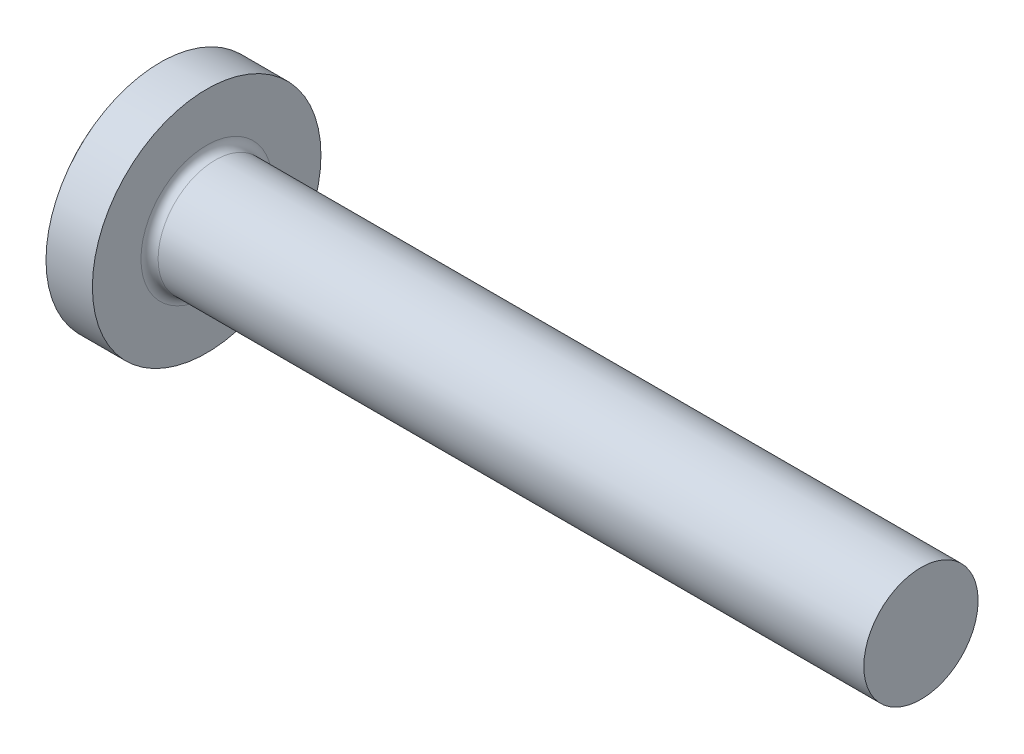
SolidWorks part; units mm, degrees
ref_plane "Front Plane" through (0, 0, 0) normal (0, 0, 1) x (1, 0, 0)
ref_plane "Top Plane" through (0, 0, 0) normal (0, 1, 0) x (1, 0, 0)
ref_plane "Right Plane" through (0, 0, 0) normal (1, 0, 0) x (0, 0, -1)
sketch "BodySke" plane through (0, 0, 0) normal (0, 0, 1) x (1, 0, 0)
  line L0 (0, 0) -> (111.3824, 0) construction
  line L1 (0, 0) -> (0, 8) construction
  line L2 (6, 4) -> (6, 8)
  line L3 (6, 8) -> (2.753, 8)
  line L4 (6, 4) -> (56, 4)
  line L5 (56, 4) -> (56, 0)
  line L6 (7.25, 7.824) -> (7.25, -6.8939) construction
  line L7 (0, 0) -> (56, 0)
  line L8 (8.5, 8.824) -> (8.5, -4.958) construction
  arc A1 (2.753, 8) -> (0, 0) centre (13, 0) ccw
  point P10 (56, 3.4455)
  dimension "Thread_minor" = 6.891
  dimension "Head_height" = 6
  dimension "Advance" = 1.25
  dimension "Length" = 50
  dimension "Head_dia" = 16
revolve "BaseBody" add sketch "BodySke" angle 360 about L0
cosmetic thread "ThreadCosmetic" [suppressed] parameters "Thread_minor"=6.891
fillet "Fillet1" radius 0.6 1 edges at (6, 0, 4)
ref_plane "Plane1" through (4.5, 0, 0) normal (1, 0, 0) x (0, 0, -1)
sketch "RecSkeTop" plane through (0, 0, 0) normal (1, 0, 0) x (0, 0, -1)
  line L1 (-0.968, 4.4) -> (0.968, 4.4)
  line L2 (-0.968, 4.4) -> (-0.968, -4.4)
  line L3 (-0.968, -4.4) -> (0.968, -4.4)
  line L4 (0.968, 4.4) -> (0.968, -4.4)
  dimension "D1" = 4.4
  dimension "D2" = 1.936
  dimension "D3" = 0.968
sketch "RecSkeBot" plane through (4.5, 0, 0) normal (1, 0, 0) x (0, 0, -1)
  line L0 (-0.968, 4.4) -> (-0.968, -4.4) construction
  line L1 (-0.968, 2.1564) -> (0.968, 2.1564)
  line L2 (-0.968, 2.1564) -> (-0.968, -2.1564)
  line L3 (-0.968, -2.1564) -> (0.968, -2.1564)
  line L4 (0.968, 2.1564) -> (0.968, -2.1564)
  line L5 (0.968, 4.4) -> (0.968, -4.4) construction
  dimension "D1" = 4.3128
  dimension "D2" = 2.1564
loft "Recess" cut profiles "RecSkeTop", "RecSkeBot" connector at (0, -4.4, 0.968) connector at (4.5, -2.1564, 0.968)
pattern_circular "RecPat" count 2 every 90 about axis through (0, 0, 0) along (1, 0, 0) of "Recess"
sketch "RecCorSke" plane through (0, 0, 0) normal (0, 0, 1) x (1, 0, 0)
  line L0 (0, 0) -> (57.5987, 0) construction
  line L1 (0, 0) -> (0, 2.1296)
  line L3 (0, 2.1296) -> (4.5, 1.8149)
  line L4 (4.5, 1.8149) -> (5.0897, 0)
  line L5 (5.0897, 0) -> (0, 0)
  dimension "D1" = 18
  dimension "D2" = 4.5
  dimension "D3" = 2.1296
  dimension "D4" = 4
revolve "RecessCore" cut sketch "RecCorSke" angle 360 about L0
sketch "ThdSchSke" plane through (0, 0, 0) normal (0, 0, 1) x (1, 0, 0)
  line L0 (0, 0) -> (55.1256, 0) construction
  line L1 (0, 0) -> (111.3824, 0) construction
  line L2 (55.6799, 4) -> (55.6799, 4.6403)
  line L3 (55.6799, 4.6403) -> (56.3201, 4.6403)
  line L4 (56.3201, 4.6403) -> (56.3201, 4)
  line L5 (56.3201, 4) -> (56, 3.4455)
  line L6 (56, 3.4455) -> (55.6799, 4)
  line L7 (6, 4) -> (56, 4) construction
  line L13 (56, 4) -> (56, 0) construction
revolve "ThreadSchematic" [suppressed] cut sketch "ThdSchSke" angle 360 about L0
pattern_linear "ThdSchPat" [suppressed] count 39 along (-1, 0, 0) of bodies 103
equation "\"Thread_minor@ThreadCosmetic\" = \"Thread_minor@BodySke\""
equation "\"D1@RecSkeTop\" = \"Cross_dia@RecSkeTop\" / 2"
equation "\"D2@RecSkeTop\" = \"Cross_dia@RecSkeTop\" * 0.22"
equation "\"D3@RecSkeTop\" = \"D2@RecSkeTop\" / 2"
equation "\"D1@RecSkeBot\" = \"Cross_dia@RecSkeTop\" - 2 * \"Cross_depth@Plane1\" *  tan( 26.5 * 0.017453292 ) "
equation "\"D2@RecSkeBot\" = \"D1@RecSkeBot\" / 2"
equation "\"D2@RecCorSke\" = \"Cross_depth@Plane1\""
equation "\"D3@RecCorSke\" = \"D2@RecSkeTop\" * 1.1"
equation "\"Advance@ThdSchPat\" = \"Advance@BodySke\""
equation "\"D1@ThdSchPat\" =  int( ( \"Length@BodySke\"-\"Thread_runout@BodySke\" )  / \"Advance@ThdSchPat\" ) + 1 "
